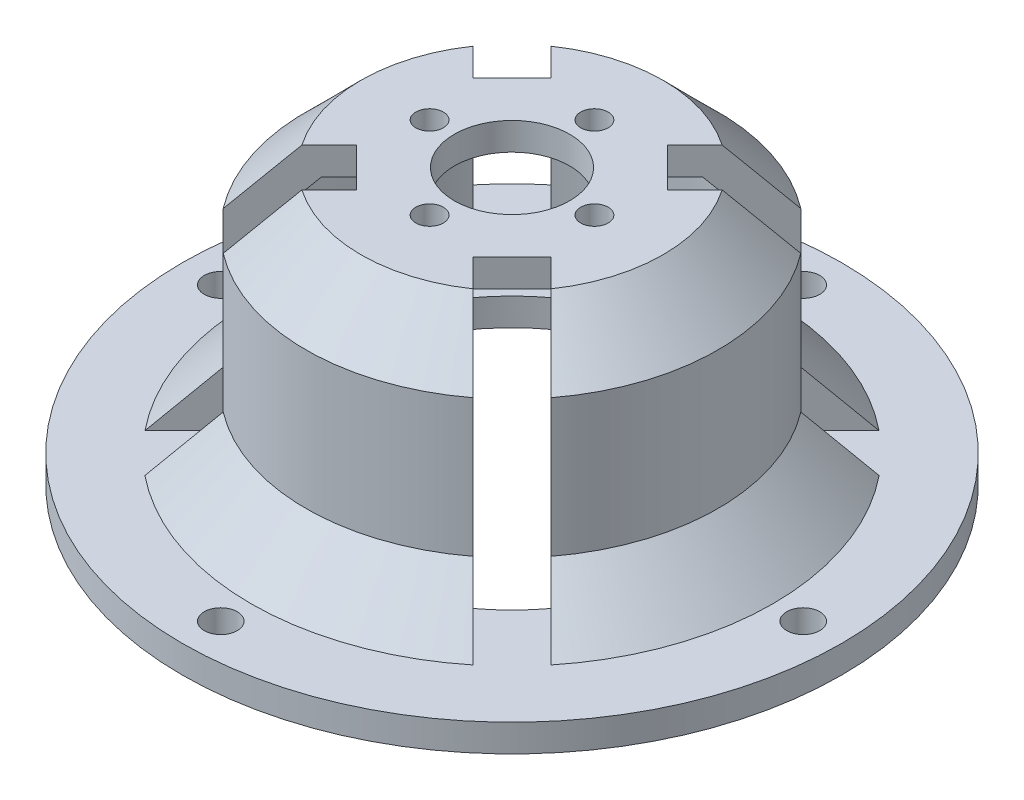
SolidWorks part; units mm, degrees
ref_plane "Front Plane" through (0, 0, 0) normal (0, 0, 1) x (1, 0, 0)
ref_plane "Top Plane" through (0, 0, 0) normal (0, 1, 0) x (1, 0, 0)
ref_plane "Right Plane" through (0, 0, 0) normal (1, 0, 0) x (0, 0, -1)
ref_axis "CentreAxist" through (0, 45.9861, 0) along (0, -1, 0)
sketch "Sketch1" plane through (0, 0, 0) normal (0, 1, 0) x (1, 0, 0)
  circle A1 centre (0, 0) radius 60
  point P8 (0, 0)
  point P14 (0, 0)
  point P15 (0, 0)
  dimension "D2" = 120
extrude "Stock" add sketch "Sketch1" against normal blind 50
sketch "Sketch7" plane through (0, 0, 0) normal (0, 1, 0) x (1, 0, 0)
  circle A0 centre (0, 0) radius 10.5
  dimension "D1" = 21
sketch "Sketch8" plane through (0, 0, 0) normal (0, 1, 0) x (1, 0, 0)
  circle A0 centre (0, 0) radius 35
  dimension "D1" = 70
extrude "HollowInterior" cut sketch "Sketch8" against normal up to next from offset 5 offset against normal yes
extrude "HoleForMotorShaft" cut sketch "Sketch7" against normal through all
sketch "Sketch9" plane through (0, 0, 0) normal (0, 1, 0) x (1, 0, 0)
  circle A0 centre (0, 0) radius 37.5
  dimension "D1" = 75
extrude "ExteriorLathe" cut sketch "Sketch9" along direction (0, 1, 0) on the side against the normal offset from surface (45 mm away) 5 from surface flip side to cut up to face at (0, -50, 35) starting at face at (0, 0, 10.5)
chamfer "Chamfer1" distance 10 angle 45 1 edges at (0, -5, 35)
chamfer "Chamfer2" distance 10 angle 45 1 edges at (0, 0, 37.5)
chamfer "Chamfer3" distance 10 angle 45 1 edges at (0, -45, 37.5)
sketch "Sketch10" plane through (0, 0, 0) normal (0, 1, 0) x (1, 0, 0)
  line L0 (-14.1421, 14.1421) -> (-33.5876, 33.5876)
  line L1 (0, 0) -> (0, 47.5) construction
  line L2 (-14.1421, 14.1421) -> (0, 0) construction
  line L3 (14.1421, 14.1421) -> (0, 0) construction
  line L4 (14.1421, 14.1421) -> (33.5876, 33.5876)
  line L5 (14.1421, -14.1421) -> (0, 0) construction
  line L6 (14.1421, -14.1421) -> (33.5876, -33.5876)
  line L7 (-14.1421, -14.1421) -> (0, 0) construction
  line L8 (-14.1421, -14.1421) -> (-33.5876, -33.5876)
  circle A1 centre (0, 0) radius 47.5 construction
  point P9 (0, 0)
  point P16 (0, 0)
  dimension "D2" = 4
  dimension "D1" = 95
  dimension "D3" = 45
extrude "SlotsForFun" cut sketch "Sketch10" against normal up to surface (45 mm away) thin up to face at (0, -45, 47.5) thin type mid plane wall 10
sketch "Sketch13" plane through (0, 0, 0) normal (0, 1, 0) x (1, 0, 0)
  line L0 (0, 0) -> (0, 15) construction
  line L1 (0, 0) -> (15, 0) construction
  line L2 (0, 0) -> (0, -15) construction
  line L3 (0, 0) -> (-15, 0) construction
  circle A0 centre (0, 15) radius 2.5
  circle A1 centre (15, 0) radius 2.5
  circle A2 centre (0, -15) radius 2.5
  circle A3 centre (-15, 0) radius 2.5
  point P13 (0, 0)
  dimension "D1" = 5
  dimension "D2" = 15
  dimension "D3" = 4
extrude "GearboxMountingHoles" cut sketch "Sketch13" against normal up to surface (5 mm away) from surface up to face at (0, -5, 10.5) starting at face at (0, 0, 10.5)
sketch "Sketch14" plane through (0, 0, 0) normal (0, 1, 0) x (1, 0, 0)
  line L0 (0, 0) -> (0, 53) construction
  line L1 (0, 0) -> (53, 0) construction
  line L2 (0, 0) -> (0, -53) construction
  line L3 (0, 0) -> (-53, 0) construction
  circle A0 centre (0, 53) radius 3
  circle A1 centre (53, 0) radius 3
  circle A2 centre (0, -53) radius 3
  circle A3 centre (-53, 0) radius 3
  point P12 (0, 0)
  dimension "D1" = 6
  dimension "D2" = 53
  dimension "D3" = 4
extrude "Cut-Extrude5" cut sketch "Sketch14" against normal up to surface (50 mm away) from surface up to face at (0, -50, 35) starting at face at (0, -45, 0)
